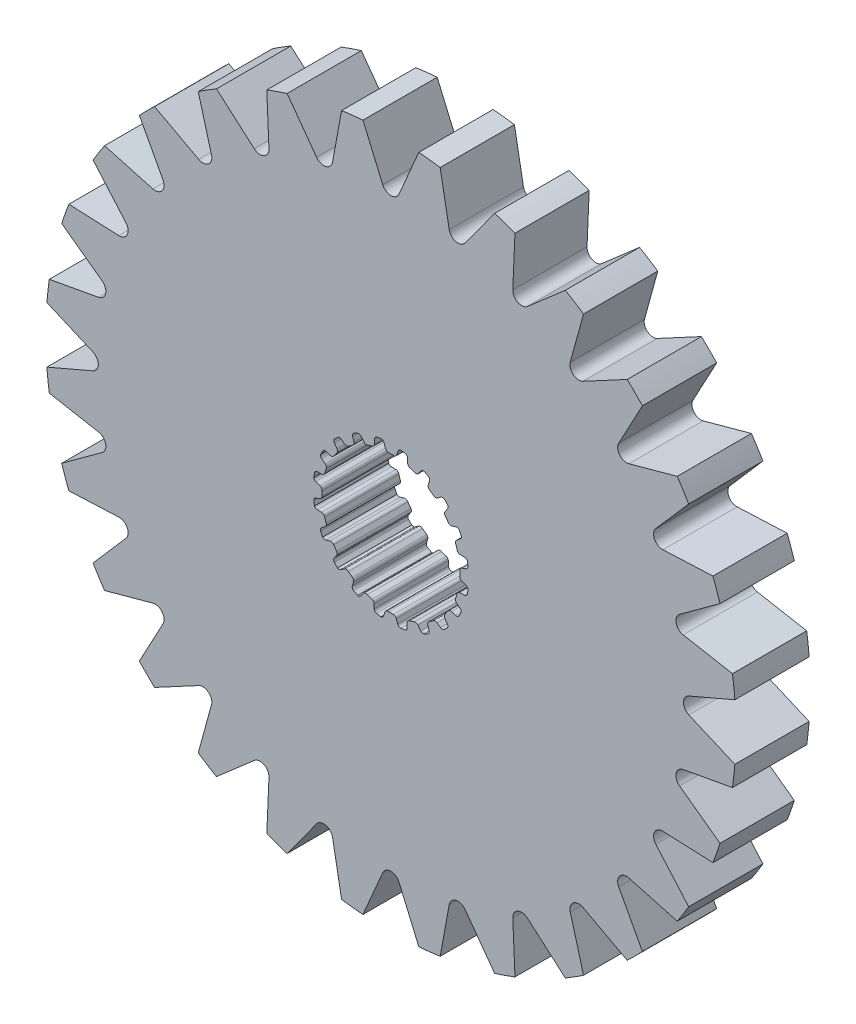
SolidWorks part; units mm, degrees
ref_plane "Front Plane" through (0, 0, 0) normal (0, 0, 1) x (1, 0, 0)
ref_plane "Top Plane" through (0, 0, 0) normal (0, 1, 0) x (1, 0, 0)
ref_plane "Right Plane" through (0, 0, 0) normal (1, 0, 0) x (0, 0, -1)
sketch "Sketch1" plane through (0, 0, 0) normal (0, 0, 1) x (1, 0, 0)
  line L0 (-0.1069, 2.9699) -> (0.1069, 2.9699)
  line L1 (0.3159, 3.2375) -> (0.2537, 3.0575)
  line L2 (-0.2964, 3.2367) -> (-0.2318, 3.0575)
  line L3 (-0.2964, 3.2367) -> (0.3159, 3.2375) construction
  line L4 (0, 3.3252) -> (0, 0) construction
  line L5 (-0.2318, 3.0575) -> (0.2537, 3.0575) construction
  line L6 (-0.4281, 3.3241) -> (0.4281, 3.3263) construction
  line L7 (0.7183, 3.1698) -> (0.7244, 2.9795)
  line L8 (0.816, 2.8576) -> (1.0195, 2.7915)
  line L9 (1.3009, 2.9815) -> (1.1862, 2.8295)
  line L10 (1.6627, 2.7927) -> (1.6097, 2.6099)
  line L11 (1.6591, 2.4655) -> (1.8322, 2.3398)
  line L12 (2.1585, 2.4335) -> (2.0025, 2.3245)
  line L13 (2.4443, 2.1423) -> (2.3374, 1.9847)
  line L14 (2.3398, 1.8322) -> (2.4655, 1.6591)
  line L15 (2.8049, 1.6474) -> (2.6228, 1.5919)
  line L16 (2.9866, 1.2821) -> (2.8363, 1.1653)
  line L17 (2.7915, 1.0195) -> (2.8576, 0.816)
  line L18 (3.1767, 0.7) -> (2.9863, 0.7035)
  line L19 (3.2367, 0.2964) -> (3.0575, 0.2318)
  line L20 (2.9699, 0.1069) -> (2.9699, -0.1069)
  line L21 (3.2375, -0.3159) -> (3.0575, -0.2537)
  line L22 (3.1698, -0.7183) -> (2.9795, -0.7244)
  line L23 (2.8576, -0.816) -> (2.7915, -1.0195)
  line L24 (2.9815, -1.3009) -> (2.8295, -1.1862)
  line L25 (2.7927, -1.6627) -> (2.6099, -1.6097)
  line L26 (2.4655, -1.6591) -> (2.3398, -1.8322)
  line L27 (2.4335, -2.1585) -> (2.3245, -2.0025)
  line L28 (2.1423, -2.4443) -> (1.9847, -2.3374)
  line L29 (1.8322, -2.3398) -> (1.6591, -2.4655)
  line L30 (1.6474, -2.8049) -> (1.5919, -2.6228)
  line L31 (1.2821, -2.9866) -> (1.1653, -2.8363)
  line L32 (1.0195, -2.7915) -> (0.816, -2.8576)
  line L33 (0.7, -3.1767) -> (0.7035, -2.9863)
  line L34 (0.2964, -3.2367) -> (0.2318, -3.0575)
  line L35 (0.1069, -2.9699) -> (-0.1069, -2.9699)
  line L36 (-0.3159, -3.2375) -> (-0.2537, -3.0575)
  line L37 (-0.7183, -3.1698) -> (-0.7244, -2.9795)
  line L38 (-0.816, -2.8576) -> (-1.0195, -2.7915)
  line L39 (-1.3009, -2.9815) -> (-1.1862, -2.8295)
  line L40 (-1.6627, -2.7927) -> (-1.6097, -2.6099)
  line L41 (-1.6591, -2.4655) -> (-1.8322, -2.3398)
  line L42 (-2.1585, -2.4335) -> (-2.0025, -2.3245)
  line L43 (-2.4443, -2.1423) -> (-2.3374, -1.9847)
  line L44 (-2.3398, -1.8322) -> (-2.4655, -1.6591)
  line L45 (-2.8049, -1.6474) -> (-2.6228, -1.5919)
  line L46 (-2.9866, -1.2821) -> (-2.8363, -1.1653)
  line L47 (-2.7915, -1.0195) -> (-2.8576, -0.816)
  line L48 (-3.1767, -0.7) -> (-2.9863, -0.7035)
  line L49 (-3.2367, -0.2964) -> (-3.0575, -0.2318)
  line L50 (-2.9699, -0.1069) -> (-2.9699, 0.1069)
  line L51 (-3.2375, 0.3159) -> (-3.0575, 0.2537)
  line L52 (-3.1698, 0.7183) -> (-2.9795, 0.7244)
  line L53 (-2.8576, 0.816) -> (-2.7915, 1.0195)
  line L54 (-2.9815, 1.3009) -> (-2.8295, 1.1862)
  line L55 (-2.7927, 1.6627) -> (-2.6099, 1.6097)
  line L56 (-2.4655, 1.6591) -> (-2.3398, 1.8322)
  line L57 (-2.4335, 2.1585) -> (-2.3245, 2.0025)
  line L58 (-2.1423, 2.4443) -> (-1.9847, 2.3374)
  line L59 (-1.8322, 2.3398) -> (-1.6591, 2.4655)
  line L60 (-1.6474, 2.8049) -> (-1.5919, 2.6228)
  line L61 (-1.2821, 2.9866) -> (-1.1653, 2.8363)
  line L62 (-1.0195, 2.7915) -> (-0.816, 2.8576)
  line L63 (-0.7, 3.1767) -> (-0.7035, 2.9863)
  line L64 (0.4281, 3.3263) -> (0.62, 3.2938)
  line L65 (1.4351, 3.0312) -> (1.6075, 2.9409)
  line L66 (2.3015, 2.4394) -> (2.4376, 2.3003)
  line L67 (2.9427, 1.6088) -> (3.0291, 1.4344)
  line L68 (3.2958, 0.6207) -> (3.3241, 0.4281)
  line L69 (3.3263, -0.4281) -> (3.2938, -0.62)
  line L70 (3.0312, -1.4351) -> (2.9409, -1.6075)
  line L71 (2.4394, -2.3015) -> (2.3003, -2.4376)
  line L72 (1.6088, -2.9427) -> (1.4344, -3.0291)
  line L73 (0.6207, -3.2958) -> (0.4281, -3.3241)
  line L74 (-0.4281, -3.3263) -> (-0.62, -3.2938)
  line L75 (-1.4351, -3.0312) -> (-1.6075, -2.9409)
  line L76 (-2.3015, -2.4394) -> (-2.4376, -2.3003)
  line L77 (-2.9427, -1.6088) -> (-3.0291, -1.4344)
  line L78 (-3.2958, -0.6207) -> (-3.3241, -0.4281)
  line L79 (-3.3263, 0.4281) -> (-3.2938, 0.62)
  line L80 (-3.0312, 1.4351) -> (-2.9409, 1.6075)
  line L81 (-2.4394, 2.3015) -> (-2.3003, 2.4376)
  line L82 (-1.6088, 2.9427) -> (-1.4344, 3.0291)
  line L83 (-0.6207, 3.2958) -> (-0.4281, 3.3241)
  arc A0 (0.2537, 3.0575) -> (0.1069, 2.9699) centre (0.1283, 3.1009) cw
  arc A1 (-0.2318, 3.0575) -> (-0.1069, 2.9699) centre (-0.1069, 3.1026) ccw
  arc A2 (0.62, 3.2938) -> (0.7183, 3.1698) centre (0.5856, 3.1656) cw
  arc A3 (0.7244, 2.9795) -> (0.816, 2.8576) centre (0.857, 2.9838) ccw
  arc A4 (-0.4281, 3.3241) -> (-0.2964, 3.2367) centre (-0.4213, 3.1916) cw
  arc A5 (0.4281, 3.3263) -> (0.3159, 3.2375) centre (0.4413, 3.1942) ccw
  arc A6 (1.1862, 2.8295) -> (1.0195, 2.7915) centre (1.0802, 2.9095) cw
  arc A7 (1.4351, 3.0312) -> (1.3009, 2.9815) centre (1.4068, 2.9015) ccw
  arc A8 (1.6075, 2.9409) -> (1.6627, 2.7927) centre (1.5352, 2.8297) cw
  arc A9 (1.6097, 2.6099) -> (1.6591, 2.4655) centre (1.7371, 2.5729) ccw
  arc A10 (2.0025, 2.3245) -> (1.8322, 2.3398) centre (1.9264, 2.4332) cw
  arc A11 (2.3015, 2.4394) -> (2.1585, 2.4335) centre (2.2346, 2.3248) ccw
  arc A12 (2.4376, 2.3003) -> (2.4443, 2.1423) centre (2.3345, 2.2168) cw
  arc A13 (2.3374, 1.9847) -> (2.3398, 1.8322) centre (2.4472, 1.9102) ccw
  arc A14 (2.6228, 1.5919) -> (2.4655, 1.6591) centre (2.5841, 1.7189) cw
  arc A15 (2.9427, 1.6088) -> (2.8049, 1.6474) centre (2.8436, 1.5205) ccw
  arc A16 (3.0291, 1.4344) -> (2.9866, 1.2821) centre (2.9052, 1.3869) cw
  arc A17 (2.8363, 1.1653) -> (2.7915, 1.0195) centre (2.9177, 1.0605) ccw
  arc A18 (2.9863, 0.7035) -> (2.8576, 0.816) centre (2.9887, 0.8362) cw
  arc A19 (3.2958, 0.6207) -> (3.1767, 0.7) centre (3.1743, 0.5673) ccw
  arc A20 (3.3241, 0.4281) -> (3.2367, 0.2964) centre (3.1916, 0.4213) cw
  arc A21 (3.0575, 0.2318) -> (2.9699, 0.1069) centre (3.1026, 0.1069) ccw
  arc A22 (3.0575, -0.2537) -> (2.9699, -0.1069) centre (3.1009, -0.1283) cw
  arc A23 (3.3263, -0.4281) -> (3.2375, -0.3159) centre (3.1942, -0.4413) ccw
  arc A24 (3.2938, -0.62) -> (3.1698, -0.7183) centre (3.1656, -0.5856) cw
  arc A25 (2.9795, -0.7244) -> (2.8576, -0.816) centre (2.9838, -0.857) ccw
  arc A26 (2.8295, -1.1862) -> (2.7915, -1.0195) centre (2.9095, -1.0802) cw
  arc A27 (3.0312, -1.4351) -> (2.9815, -1.3009) centre (2.9015, -1.4068) ccw
  arc A28 (2.9409, -1.6075) -> (2.7927, -1.6627) centre (2.8297, -1.5352) cw
  arc A29 (2.6099, -1.6097) -> (2.4655, -1.6591) centre (2.5729, -1.7371) ccw
  arc A30 (2.3245, -2.0025) -> (2.3398, -1.8322) centre (2.4332, -1.9264) cw
  arc A31 (2.4394, -2.3015) -> (2.4335, -2.1585) centre (2.3248, -2.2346) ccw
  arc A32 (2.3003, -2.4376) -> (2.1423, -2.4443) centre (2.2168, -2.3345) cw
  arc A33 (1.9847, -2.3374) -> (1.8322, -2.3398) centre (1.9102, -2.4472) ccw
  arc A34 (1.5919, -2.6228) -> (1.6591, -2.4655) centre (1.7189, -2.5841) cw
  arc A35 (1.6088, -2.9427) -> (1.6474, -2.8049) centre (1.5205, -2.8436) ccw
  arc A36 (1.4344, -3.0291) -> (1.2821, -2.9866) centre (1.3869, -2.9052) cw
  arc A37 (1.1653, -2.8363) -> (1.0195, -2.7915) centre (1.0605, -2.9177) ccw
  arc A38 (0.7035, -2.9863) -> (0.816, -2.8576) centre (0.8362, -2.9887) cw
  arc A39 (0.6207, -3.2958) -> (0.7, -3.1767) centre (0.5673, -3.1743) ccw
  arc A40 (0.4281, -3.3241) -> (0.2964, -3.2367) centre (0.4213, -3.1916) cw
  arc A41 (0.2318, -3.0575) -> (0.1069, -2.9699) centre (0.1069, -3.1026) ccw
  arc A42 (-0.2537, -3.0575) -> (-0.1069, -2.9699) centre (-0.1283, -3.1009) cw
  arc A43 (-0.4281, -3.3263) -> (-0.3159, -3.2375) centre (-0.4413, -3.1942) ccw
  arc A44 (-0.62, -3.2938) -> (-0.7183, -3.1698) centre (-0.5856, -3.1656) cw
  arc A45 (-0.7244, -2.9795) -> (-0.816, -2.8576) centre (-0.857, -2.9838) ccw
  arc A46 (-1.1862, -2.8295) -> (-1.0195, -2.7915) centre (-1.0802, -2.9095) cw
  arc A47 (-1.4351, -3.0312) -> (-1.3009, -2.9815) centre (-1.4068, -2.9015) ccw
  arc A48 (-1.6075, -2.9409) -> (-1.6627, -2.7927) centre (-1.5352, -2.8297) cw
  arc A49 (-1.6097, -2.6099) -> (-1.6591, -2.4655) centre (-1.7371, -2.5729) ccw
  arc A50 (-2.0025, -2.3245) -> (-1.8322, -2.3398) centre (-1.9264, -2.4332) cw
  arc A51 (-2.3015, -2.4394) -> (-2.1585, -2.4335) centre (-2.2346, -2.3248) ccw
  arc A52 (-2.4376, -2.3003) -> (-2.4443, -2.1423) centre (-2.3345, -2.2168) cw
  arc A53 (-2.3374, -1.9847) -> (-2.3398, -1.8322) centre (-2.4472, -1.9102) ccw
  arc A54 (-2.6228, -1.5919) -> (-2.4655, -1.6591) centre (-2.5841, -1.7189) cw
  arc A55 (-2.9427, -1.6088) -> (-2.8049, -1.6474) centre (-2.8436, -1.5205) ccw
  arc A56 (-3.0291, -1.4344) -> (-2.9866, -1.2821) centre (-2.9052, -1.3869) cw
  arc A57 (-2.8363, -1.1653) -> (-2.7915, -1.0195) centre (-2.9177, -1.0605) ccw
  arc A58 (-2.9863, -0.7035) -> (-2.8576, -0.816) centre (-2.9887, -0.8362) cw
  arc A59 (-3.2958, -0.6207) -> (-3.1767, -0.7) centre (-3.1743, -0.5673) ccw
  arc A60 (-3.3241, -0.4281) -> (-3.2367, -0.2964) centre (-3.1916, -0.4213) cw
  arc A61 (-3.0575, -0.2318) -> (-2.9699, -0.1069) centre (-3.1026, -0.1069) ccw
  arc A62 (-3.0575, 0.2537) -> (-2.9699, 0.1069) centre (-3.1009, 0.1283) cw
  arc A63 (-3.3263, 0.4281) -> (-3.2375, 0.3159) centre (-3.1942, 0.4413) ccw
  arc A64 (-3.2938, 0.62) -> (-3.1698, 0.7183) centre (-3.1656, 0.5856) cw
  arc A65 (-2.9795, 0.7244) -> (-2.8576, 0.816) centre (-2.9838, 0.857) ccw
  arc A66 (-2.8295, 1.1862) -> (-2.7915, 1.0195) centre (-2.9095, 1.0802) cw
  arc A67 (-3.0312, 1.4351) -> (-2.9815, 1.3009) centre (-2.9015, 1.4068) ccw
  arc A68 (-2.9409, 1.6075) -> (-2.7927, 1.6627) centre (-2.8297, 1.5352) cw
  arc A69 (-2.6099, 1.6097) -> (-2.4655, 1.6591) centre (-2.5729, 1.7371) ccw
  arc A70 (-2.3245, 2.0025) -> (-2.3398, 1.8322) centre (-2.4332, 1.9264) cw
  arc A71 (-2.4394, 2.3015) -> (-2.4335, 2.1585) centre (-2.3248, 2.2346) ccw
  arc A72 (-2.3003, 2.4376) -> (-2.1423, 2.4443) centre (-2.2168, 2.3345) cw
  arc A73 (-1.9847, 2.3374) -> (-1.8322, 2.3398) centre (-1.9102, 2.4472) ccw
  arc A74 (-1.5919, 2.6228) -> (-1.6591, 2.4655) centre (-1.7189, 2.5841) cw
  arc A75 (-1.6088, 2.9427) -> (-1.6474, 2.8049) centre (-1.5205, 2.8436) ccw
  arc A76 (-1.4344, 3.0291) -> (-1.2821, 2.9866) centre (-1.3869, 2.9052) cw
  arc A77 (-1.1653, 2.8363) -> (-1.0195, 2.7915) centre (-1.0605, 2.9177) ccw
  arc A78 (-0.7035, 2.9863) -> (-0.816, 2.8576) centre (-0.8362, 2.9887) cw
  arc A79 (-0.6207, 3.2958) -> (-0.7, 3.1767) centre (-0.5673, 3.1743) ccw
  circle A80 centre (0, 0) radius 14.877
  point P14 (0, 2.9699)
  point P247 (0, 0)
  dimension "D4" = 0.1327
  dimension "D8" = 20
  dimension "D9" = 29.754
  dimension "D1" = 2.9699
  dimension "D2" = 0.2139
  dimension "D3" = 0.1904
  dimension "D5" = 0.0877
  dimension "D6" = 0.4855
  dimension "D7" = 0.8563
extrude "Boss-Extrude1" add sketch "Sketch1" along normal mid plane 3.2004
sketch "Sketch2" plane through (0, 0, 1.6002) normal (0, 0, 1) x (1, 0, 0)
  line L0 (0, 14.8282) -> (0, 0) construction
  line L1 (1.557, 27.6728) -> (0, 0) construction
  line L2 (-1.204, 14.8282) -> (1.204, 14.8282) construction
  line L3 (-0.7785, 13.8364) -> (0.7785, 13.8364) construction
  line L4 (-1.204, 14.8282) -> (-0.353, 12.8446)
  line L5 (1.204, 14.8282) -> (0.353, 12.8446)
  line L6 (4.4734, 14.1885) -> (3.2023, 12.444)
  line L7 (2.1258, 14.7243) -> (2.514, 12.6011)
  line L8 (7.5185, 12.8373) -> (5.8911, 11.4194)
  line L9 (5.3489, 13.8821) -> (5.255, 11.7257)
  line L10 (10.1866, 10.8425) -> (8.2845, 9.8222)
  line L11 (8.3039, 12.3438) -> (7.7325, 10.2624)
  line L12 (12.3438, 8.3039) -> (10.2624, 7.7325)
  line L13 (10.8425, 10.1866) -> (9.8222, 8.2845)
  line L14 (13.8821, 5.3489) -> (11.7257, 5.255)
  line L15 (12.8373, 7.5185) -> (11.4194, 5.8911)
  line L16 (14.7243, 2.1258) -> (12.6011, 2.514)
  line L17 (14.1885, 4.4734) -> (12.444, 3.2023)
  line L18 (14.8282, -1.204) -> (12.8446, -0.353)
  line L19 (14.8282, 1.204) -> (12.8446, 0.353)
  line L20 (14.1885, -4.4734) -> (12.444, -3.2023)
  line L21 (14.7243, -2.1258) -> (12.6011, -2.514)
  line L22 (12.8373, -7.5185) -> (11.4194, -5.8911)
  line L23 (13.8821, -5.3489) -> (11.7257, -5.255)
  line L24 (10.8425, -10.1866) -> (9.8222, -8.2845)
  line L25 (12.3438, -8.3039) -> (10.2624, -7.7325)
  line L26 (8.3039, -12.3438) -> (7.7325, -10.2624)
  line L27 (10.1866, -10.8425) -> (8.2845, -9.8222)
  line L28 (5.3489, -13.8821) -> (5.255, -11.7257)
  line L29 (7.5185, -12.8373) -> (5.8911, -11.4194)
  line L30 (2.1258, -14.7243) -> (2.514, -12.6011)
  line L31 (4.4734, -14.1885) -> (3.2023, -12.444)
  line L32 (-1.204, -14.8282) -> (-0.353, -12.8446)
  line L33 (1.204, -14.8282) -> (0.353, -12.8446)
  line L34 (-4.4734, -14.1885) -> (-3.2023, -12.444)
  line L35 (-2.1258, -14.7243) -> (-2.514, -12.6011)
  line L36 (-7.5185, -12.8373) -> (-5.8911, -11.4194)
  line L37 (-5.3489, -13.8821) -> (-5.255, -11.7257)
  line L38 (-10.1866, -10.8425) -> (-8.2845, -9.8222)
  line L39 (-8.3039, -12.3438) -> (-7.7325, -10.2624)
  line L40 (-12.3438, -8.3039) -> (-10.2624, -7.7325)
  line L41 (-10.8425, -10.1866) -> (-9.8222, -8.2845)
  line L42 (-13.8821, -5.3489) -> (-11.7257, -5.255)
  line L43 (-12.8373, -7.5185) -> (-11.4194, -5.8911)
  line L44 (-14.7243, -2.1258) -> (-12.6011, -2.514)
  line L45 (-14.1885, -4.4734) -> (-12.444, -3.2023)
  line L46 (-14.8282, 1.204) -> (-12.8446, 0.353)
  line L47 (-14.8282, -1.204) -> (-12.8446, -0.353)
  line L48 (-14.1885, 4.4734) -> (-12.444, 3.2023)
  line L49 (-14.7243, 2.1258) -> (-12.6011, 2.514)
  line L50 (-12.8373, 7.5185) -> (-11.4194, 5.8911)
  line L51 (-13.8821, 5.3489) -> (-11.7257, 5.255)
  line L52 (-10.8425, 10.1866) -> (-9.8222, 8.2845)
  line L53 (-12.3438, 8.3039) -> (-10.2624, 7.7325)
  line L54 (-8.3039, 12.3438) -> (-7.7325, 10.2624)
  line L55 (-10.1866, 10.8425) -> (-8.2845, 9.8222)
  line L56 (-5.3489, 13.8821) -> (-5.255, 11.7257)
  line L57 (-7.5185, 12.8373) -> (-5.8911, 11.4194)
  line L58 (-2.1258, 14.7243) -> (-2.514, 12.6011)
  line L59 (-4.4734, 14.1885) -> (-3.2023, 12.444)
  circle A0 centre (0, 0) radius 14.877 construction
  arc A1 (-0.353, 12.8446) -> (0.353, 12.8446) centre (0, 12.996) ccw
  arc A2 (-1.204, 14.8282) -> (1.204, 14.8282) centre (0, 0) cw
  arc A3 (2.1258, 14.7243) -> (4.4734, 14.1885) centre (0, 0) cw
  arc A4 (2.514, 12.6011) -> (3.2023, 12.444) centre (2.8919, 12.6702) ccw
  arc A5 (5.3489, 13.8821) -> (7.5185, 12.8373) centre (0, 0) cw
  arc A6 (5.255, 11.7257) -> (5.8911, 11.4194) centre (5.6388, 11.709) ccw
  arc A7 (8.3039, 12.3438) -> (10.1866, 10.8425) centre (0, 0) cw
  arc A8 (7.7325, 10.2624) -> (8.2845, 9.8222) centre (8.1029, 10.1607) ccw
  arc A9 (10.8425, 10.1866) -> (12.3438, 8.3039) centre (0, 0) cw
  arc A10 (9.8222, 8.2845) -> (10.2624, 7.7325) centre (10.1607, 8.1029) ccw
  arc A11 (12.8373, 7.5185) -> (13.8821, 5.3489) centre (0, 0) cw
  arc A12 (11.4194, 5.8911) -> (11.7257, 5.255) centre (11.709, 5.6388) ccw
  arc A13 (14.1885, 4.4734) -> (14.7243, 2.1258) centre (0, 0) cw
  arc A14 (12.444, 3.2023) -> (12.6011, 2.514) centre (12.6702, 2.8919) ccw
  arc A15 (14.8282, 1.204) -> (14.8282, -1.204) centre (0, 0) cw
  arc A16 (12.8446, 0.353) -> (12.8446, -0.353) centre (12.996, 0) ccw
  arc A17 (14.7243, -2.1258) -> (14.1885, -4.4734) centre (0, 0) cw
  arc A18 (12.6011, -2.514) -> (12.444, -3.2023) centre (12.6702, -2.8919) ccw
  arc A19 (13.8821, -5.3489) -> (12.8373, -7.5185) centre (0, 0) cw
  arc A20 (11.7257, -5.255) -> (11.4194, -5.8911) centre (11.709, -5.6388) ccw
  arc A21 (12.3438, -8.3039) -> (10.8425, -10.1866) centre (0, 0) cw
  arc A22 (10.2624, -7.7325) -> (9.8222, -8.2845) centre (10.1607, -8.1029) ccw
  arc A23 (10.1866, -10.8425) -> (8.3039, -12.3438) centre (0, 0) cw
  arc A24 (8.2845, -9.8222) -> (7.7325, -10.2624) centre (8.1029, -10.1607) ccw
  arc A25 (7.5185, -12.8373) -> (5.3489, -13.8821) centre (0, 0) cw
  arc A26 (5.8911, -11.4194) -> (5.255, -11.7257) centre (5.6388, -11.709) ccw
  arc A27 (4.4734, -14.1885) -> (2.1258, -14.7243) centre (0, 0) cw
  arc A28 (3.2023, -12.444) -> (2.514, -12.6011) centre (2.8919, -12.6702) ccw
  arc A29 (1.204, -14.8282) -> (-1.204, -14.8282) centre (0, 0) cw
  arc A30 (0.353, -12.8446) -> (-0.353, -12.8446) centre (0, -12.996) ccw
  arc A31 (-2.1258, -14.7243) -> (-4.4734, -14.1885) centre (0, 0) cw
  arc A32 (-2.514, -12.6011) -> (-3.2023, -12.444) centre (-2.8919, -12.6702) ccw
  arc A33 (-5.3489, -13.8821) -> (-7.5185, -12.8373) centre (0, 0) cw
  arc A34 (-5.255, -11.7257) -> (-5.8911, -11.4194) centre (-5.6388, -11.709) ccw
  arc A35 (-8.3039, -12.3438) -> (-10.1866, -10.8425) centre (0, 0) cw
  arc A36 (-7.7325, -10.2624) -> (-8.2845, -9.8222) centre (-8.1029, -10.1607) ccw
  arc A37 (-10.8425, -10.1866) -> (-12.3438, -8.3039) centre (0, 0) cw
  arc A38 (-9.8222, -8.2845) -> (-10.2624, -7.7325) centre (-10.1607, -8.1029) ccw
  arc A39 (-12.8373, -7.5185) -> (-13.8821, -5.3489) centre (0, 0) cw
  arc A40 (-11.4194, -5.8911) -> (-11.7257, -5.255) centre (-11.709, -5.6388) ccw
  arc A41 (-14.1885, -4.4734) -> (-14.7243, -2.1258) centre (0, 0) cw
  arc A42 (-12.444, -3.2023) -> (-12.6011, -2.514) centre (-12.6702, -2.8919) ccw
  arc A43 (-14.8282, -1.204) -> (-14.8282, 1.204) centre (0, 0) cw
  arc A44 (-12.8446, -0.353) -> (-12.8446, 0.353) centre (-12.996, 0) ccw
  arc A45 (-14.7243, 2.1258) -> (-14.1885, 4.4734) centre (0, 0) cw
  arc A46 (-12.6011, 2.514) -> (-12.444, 3.2023) centre (-12.6702, 2.8919) ccw
  arc A47 (-13.8821, 5.3489) -> (-12.8373, 7.5185) centre (0, 0) cw
  arc A48 (-11.7257, 5.255) -> (-11.4194, 5.8911) centre (-11.709, 5.6388) ccw
  arc A49 (-12.3438, 8.3039) -> (-10.8425, 10.1866) centre (0, 0) cw
  arc A50 (-10.2624, 7.7325) -> (-9.8222, 8.2845) centre (-10.1607, 8.1029) ccw
  arc A51 (-10.1866, 10.8425) -> (-8.3039, 12.3438) centre (0, 0) cw
  arc A52 (-8.2845, 9.8222) -> (-7.7325, 10.2624) centre (-8.1029, 10.1607) ccw
  arc A53 (-7.5185, 12.8373) -> (-5.3489, 13.8821) centre (0, 0) cw
  arc A54 (-5.8911, 11.4194) -> (-5.255, 11.7257) centre (-5.6388, 11.709) ccw
  arc A55 (-4.4734, 14.1885) -> (-2.1258, 14.7243) centre (0, 0) cw
  arc A56 (-3.2023, 12.444) -> (-2.514, 12.6011) centre (-2.8919, 12.6702) ccw
  point P9 (0, 13.8364)
  point P132 (0, 0)
  dimension "D1" = 0.9918
  dimension "D2" = 1.557
  dimension "D3" = 20
  dimension "D4" = 28
extrude "Cut-Extrude1" cut sketch "Sketch2" against normal up to surface (3.2004 mm away) up to face at (14.877, 0, -1.6002)
sketch "Sketch3" plane through (0, 0, 1.6002) normal (0, 0, 1) x (1, 0, 0)
  circle A0 centre (0, 0) radius 13.8852 construction
  circle A1 centre (0, 0) radius 14.877 construction
  dimension "D1" = 27.7704
